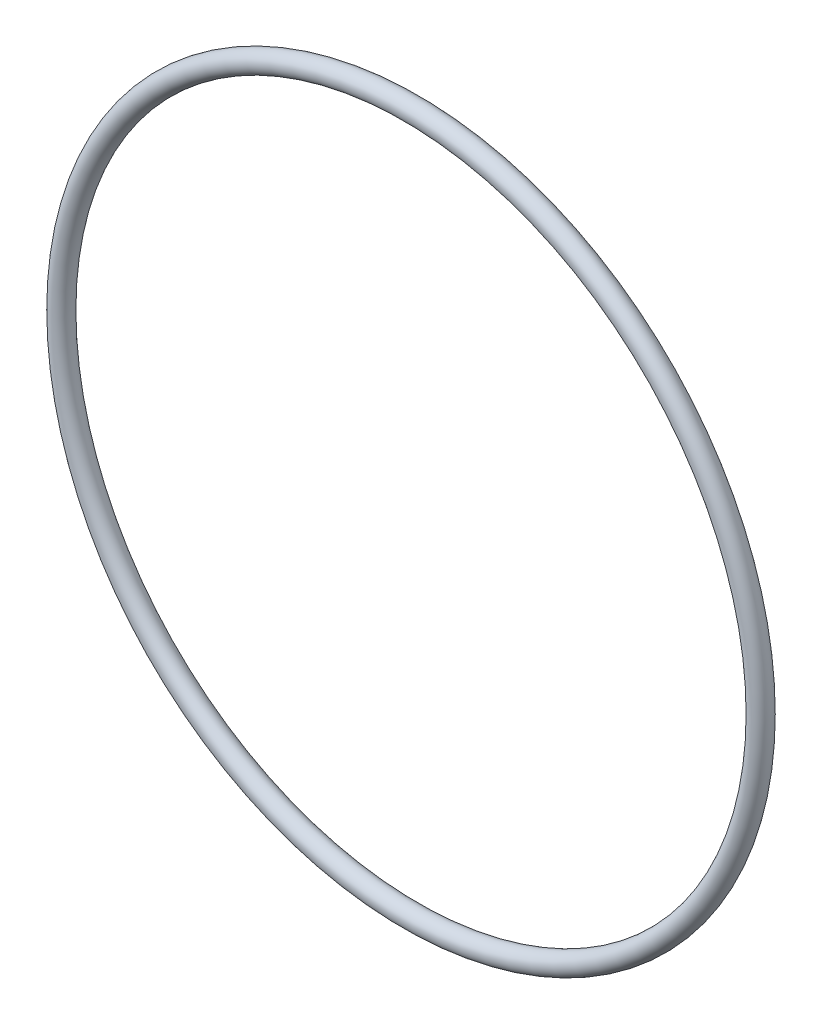
SolidWorks part; units mm, degrees
ref_plane "Front" through (0, 0, 0) normal (0, 0, 1) x (1, 0, 0)
ref_plane "Top" through (0, 0, 0) normal (0, 1, 0) x (1, 0, 0)
ref_plane "Right" through (0, 0, 0) normal (1, 0, 0) x (0, 0, -1)
ref_axis "CL" through (0, 0, -0.825) along (0, 0, 1)
sketch "Sketch1" plane through (0, 0, 0) normal (1, 0, 0) x (0, -1, 0)
  line L0 (0, -0.7267) -> (0, 0.7267) construction
  line L2 (-27.7291, 0) -> (27.7291, 0) construction
  line L3 (-23.9, 0) -> (23.9, 0) construction
  circle A0 centre (24.6266, 0) radius 0.7266
  point P9 (23.9, 0)
  point P10 (25.3533, 0)
  point P13 (24.6266, 0.7267)
  point P14 (24.6266, -0.7267)
  dimension "Width" = 1.4533
  dimension "ID" = 47.8
  dimension "OD" = 50.7066
sketch "Sketch2" plane through (0, 0, 0) normal (1, 0, 0) x (0, 0, -1)
  line L0 (-0.7267, 0) -> (0.7267, 0) construction
  line L1 (-0.7267, 0) -> (0.7267, 0) construction
  circle A0 centre (0, -24.6266) radius 0.7266 construction
  circle A1 centre (0, -24.6266) radius 0.7266
revolve "Revolve1" add sketch "Sketch2" angle 360 about L1
